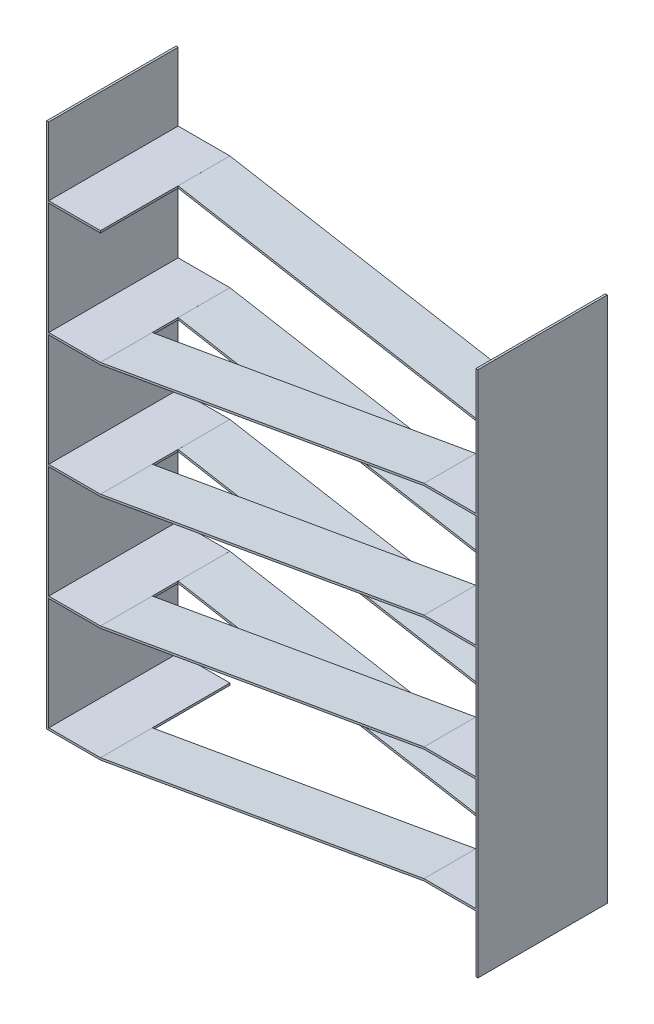
SolidWorks part; units mm, degrees
ref_plane "Front Plane" through (0, 0, 0) normal (0, 0, 1) x (1, 0, 0)
ref_plane "Top Plane" through (0, 0, 0) normal (0, 1, 0) x (1, 0, 0)
ref_plane "Right Plane" through (0, 0, 0) normal (1, 0, 0) x (0, 0, -1)
sketch "Sketch4" plane through (0, 0, 0) normal (0, 0, 1) x (1, 0, 0)
  line L0 (69.9055, -21.0836) -> (819.9055, 111.1616)
  line L1 (-0.9449, -21.0836) -> (124.2921, -21.0836) construction
  line L2 (819.9055, 0) -> (819.9055, 29.7171) construction
  line L3 (69.9055, 0) -> (69.9055, 110.7916) construction
  line L4 (819.9055, 111.1616) -> (819.9055, 115.9216)
  line L5 (819.9055, 115.9216) -> (69.9055, -16.3236)
  line L6 (69.9055, -16.3236) -> (69.9055, -21.0836)
  line L7 (819.9055, 111.1616) -> (69.9055, 111.1616) construction
  line L8 (69.9055, 243.4069) -> (69.9055, 248.1669)
  line L9 (69.9055, 248.1764) -> (69.9055, 243.4164)
  line L10 (819.9055, 380.4216) -> (69.9055, 248.1764)
  line L11 (69.9055, 243.4164) -> (819.9055, 375.6616)
  line L12 (819.9055, 111.1616) -> (69.9055, 243.4069)
  line L13 (819.9055, 115.9216) -> (69.9055, 248.1669)
  line L14 (819.9055, 375.6616) -> (819.9055, 380.4216)
  line L15 (819.9055, 375.6616) -> (69.9055, 507.9069)
  line L16 (819.9055, 380.4216) -> (69.9055, 512.6669)
  line L17 (69.9055, 507.9069) -> (69.9055, 512.6669)
  line L18 (69.9055, 512.6764) -> (69.9055, 507.9164)
  line L19 (819.9055, 644.9216) -> (69.9055, 512.6764)
  line L20 (69.9055, 507.9164) -> (819.9055, 640.1616)
  line L21 (819.9055, 640.1616) -> (819.9055, 644.9216)
  line L22 (819.9055, 640.1616) -> (69.9055, 772.4069)
  line L23 (819.9055, 644.9216) -> (69.9055, 777.1669)
  line L24 (69.9055, 772.4069) -> (69.9055, 777.1669)
  line L25 (69.9055, 777.1764) -> (69.9055, 772.4164)
  line L26 (819.9055, 909.4216) -> (69.9055, 777.1764)
  line L27 (69.9055, 772.4164) -> (819.9055, 904.6616)
  line L28 (819.9055, 904.6616) -> (819.9055, 909.4216)
  line L29 (819.9055, 904.6616) -> (69.9055, 1036.9069)
  line L30 (819.9055, 909.4216) -> (69.9055, 1041.6669)
  line L31 (69.9055, 1036.9069) -> (69.9055, 1041.6669)
  line L32 (69.9055, 248.1764) -> (-50.0945, 248.1764)
  line L33 (819.9055, 115.9216) -> (939.9055, 115.9216)
  line L34 (819.9055, 115.9216) -> (819.9055, 111.1616)
  line L35 (819.9055, 111.1616) -> (939.9055, 111.1616)
  line L36 (939.9055, 115.9216) -> (939.9055, 111.1616)
  line L37 (69.9055, -16.3236) -> (-50.0945, -16.3236)
  line L38 (69.9055, -16.3236) -> (69.9055, -21.0836)
  line L39 (69.9055, -21.0836) -> (-50.0945, -21.0836)
  line L40 (-50.0945, -16.3236) -> (-50.0945, -21.0836)
  line L41 (69.9055, 243.4164) -> (-50.0945, 243.4164)
  line L42 (-50.0945, 248.1764) -> (-50.0945, 243.4164)
  line L43 (69.9055, 248.1764) -> (69.9055, 243.4164)
  line L44 (819.9055, 375.6616) -> (819.9055, 380.4216)
  line L45 (819.9055, 375.6616) -> (939.9055, 375.6616)
  line L46 (819.9055, 380.4216) -> (939.9055, 380.4216)
  line L47 (939.9055, 380.4216) -> (939.9055, 375.6616)
  line L48 (69.9055, 512.6764) -> (-50.0945, 512.6764)
  line L49 (69.9055, 507.9164) -> (-50.0945, 507.9164)
  line L50 (-50.0945, 512.6764) -> (-50.0945, 507.9164)
  line L51 (69.9055, 512.6764) -> (69.9055, 507.9164)
  line L52 (819.9055, 640.1616) -> (819.9055, 644.9216)
  line L53 (819.9055, 640.1616) -> (939.9055, 640.1616)
  line L54 (819.9055, 644.9216) -> (939.9055, 644.9216)
  line L55 (939.9055, 644.9216) -> (939.9055, 640.1616)
  line L56 (69.9055, 777.1764) -> (-50.0945, 777.1764)
  line L57 (69.9055, 772.4164) -> (-50.0945, 772.4164)
  line L58 (-50.0945, 777.1764) -> (-50.0945, 772.4164)
  line L59 (69.9055, 777.1764) -> (69.9055, 772.4164)
  line L60 (819.9055, 904.6616) -> (819.9055, 909.4216)
  line L61 (819.9055, 904.6616) -> (939.9055, 904.6616)
  line L62 (819.9055, 909.4216) -> (939.9055, 909.4216)
  line L63 (939.9055, 909.4216) -> (939.9055, 904.6616)
  line L64 (69.9055, 1041.6764) -> (-50.0945, 1041.6764)
  line L65 (69.9055, 1036.9164) -> (-50.0945, 1036.9164)
  line L66 (-50.0945, 1041.6764) -> (-50.0945, 1036.9164)
  line L67 (69.9055, 1041.6764) -> (69.9055, 1036.9164)
  line L72 (819.9055, 1169.1616) -> (819.9055, 1173.9216) [skipped]
  line L73 (819.9055, 1169.1616) -> (939.9055, 1169.1616) [skipped]
  line L74 (819.9055, 1173.9216) -> (939.9055, 1173.9216) [skipped]
  line L75 (939.9055, 1173.9216) -> (939.9055, 1169.1616) [skipped]
  dimension "D1" = 750
  dimension "D2" = 4.76
  dimension "D3" = 10
  dimension "D5" = 4
  dimension "D4" = 10
  dimension "D6" = 264.5
  dimension "D7" = 120
  dimension "D8" = 5
extrude "Boss-Extrude6" add sketch "Sketch4" against normal blind 300 contours L37 L40 L39 L6 | L32 L42 L41 L8 L9 | L48 L50 L49 L17 L18 | L67 L64 L66 L65 L31 | L63 L62 L28 L61 | L55 L54 L21 L53 | L36 L33 L4 L35 | L56 L58 L57 L59 | L46 L47 L45 L44 region at (9.9055, -18.7036, 0) region at (879.9055, 113.5416, 0) region at (9.9055, 245.7964, 0) region at (9.9055, 510.2964, 0) region at (879.9055, 642.5416, 0) region at (879.9055, 907.0416, 0) region at (9.9055, 1039.2964, 0)
extrude "Boss-Extrude7" add sketch "Sketch4<3>" against normal blind 120 contours L0 L12 L5 L6 | L11 L15 L10 L9 L13 | L20 L22 L19 L18 L16 | L27 L29 L26 L25 L23 | L17 L20 L16 | L11 L13 L8 | L12 L4 L5 | L15 L14 L10 | L22 L21 L19 | L29 L28 L26 | L24 L27 L23 region at (441.5413, 46.8186, 0) region at (815.4063, 113.5416, 0) region at (444.892, 311.9166, 0) region at (74.3957, 245.7916, 0) region at (815.4063, 378.0416, 0) region at (74.3957, 510.2916, 0) region at (444.892, 576.4166, 0) region at (815.4063, 642.5416, 0) region at (74.3957, 774.7916, 0) region at (444.892, 840.9166, 0) region at (815.4063, 907.0416, 0)
sketch "Sketch4<3>" plane through (0, 0, 0) normal (0, 0, 1) x (1, 0, 0) same geometry as "Sketch4"
extrude "Boss-Extrude8" add sketch "Sketch4<4>" against normal blind 120 from offset 180 contours L5 L13 L11 L8 L12 | L12 L4 L5 | L11 L13 L8 | L20 L17 L15 L10 L16 | L15 L14 L10 | L17 L20 L16 | L22 L21 L19 | L27 L24 L22 L19 L23 | L24 L27 L23 | L29 L28 L26 | L31 L29 L26 L30 region at (815.4063, 113.5416, 0) region at (444.892, 179.6666, 0) region at (74.3957, 245.7916, 0) region at (815.4063, 378.0416, 0) region at (444.892, 444.1666, 0) region at (74.3957, 510.2916, 0) region at (815.4063, 642.5416, 0) region at (444.892, 708.6666, 0) region at (74.3957, 774.7916, 0) region at (815.4063, 907.0416, 0) region at (441.5413, 973.7646, 0) offset against normal yes
sketch "Sketch4<4>" plane through (0, 0, 0) normal (0, 0, 1) x (1, 0, 0) same geometry as "Sketch4"
sketch "Sketch5" plane through (0, 0, 0) normal (1, 0, 0) x (0, 0, -1)
  line L1 (0, -21.0836) -> (300, -21.0836)
  line L2 (0, -21.0836) -> (0, 1200)
  line L3 (0, 1200) -> (300, 1200)
  line L4 (300, -21.0836) -> (300, 1200)
extrude "Boss-Extrude10" add sketch "Sketch5" against normal blind 4.76 from offset 50 separate body contours L1 L4 L3 L2 region at (0, 589.4582, -150) offset against normal yes
extrude "Boss-Extrude11" add sketch "Sketch5<3>" along normal blind 4.76 from offset 940 separate body
sketch "Sketch5<3>" plane through (0, 0, 0) normal (1, 0, 0) x (0, 0, -1) same geometry as "Sketch5"
